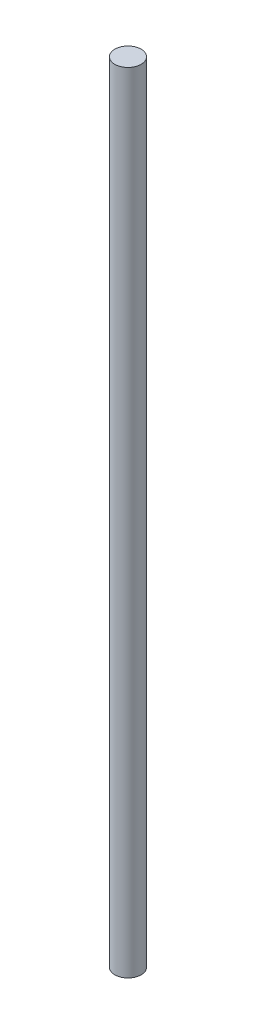
SolidWorks part; units mm, degrees
ref_plane "Front Plane" through (0, 0, 0) normal (0, 0, 1) x (1, 0, 0)
ref_plane "Top Plane" through (0, 0, 0) normal (0, 1, 0) x (1, 0, 0)
ref_plane "Right Plane" through (0, 0, 0) normal (1, 0, 0) x (0, 0, -1)
sketch "Sketch1" plane through (0, 0, 0) normal (0, 1, 0) x (1, 0, 0)
  circle A0 centre (0, 0) radius 2
  dimension "D1" = 4
extrude "Boss-Extrude1" add sketch "Sketch1" along normal blind 60 and the other way blind 60
